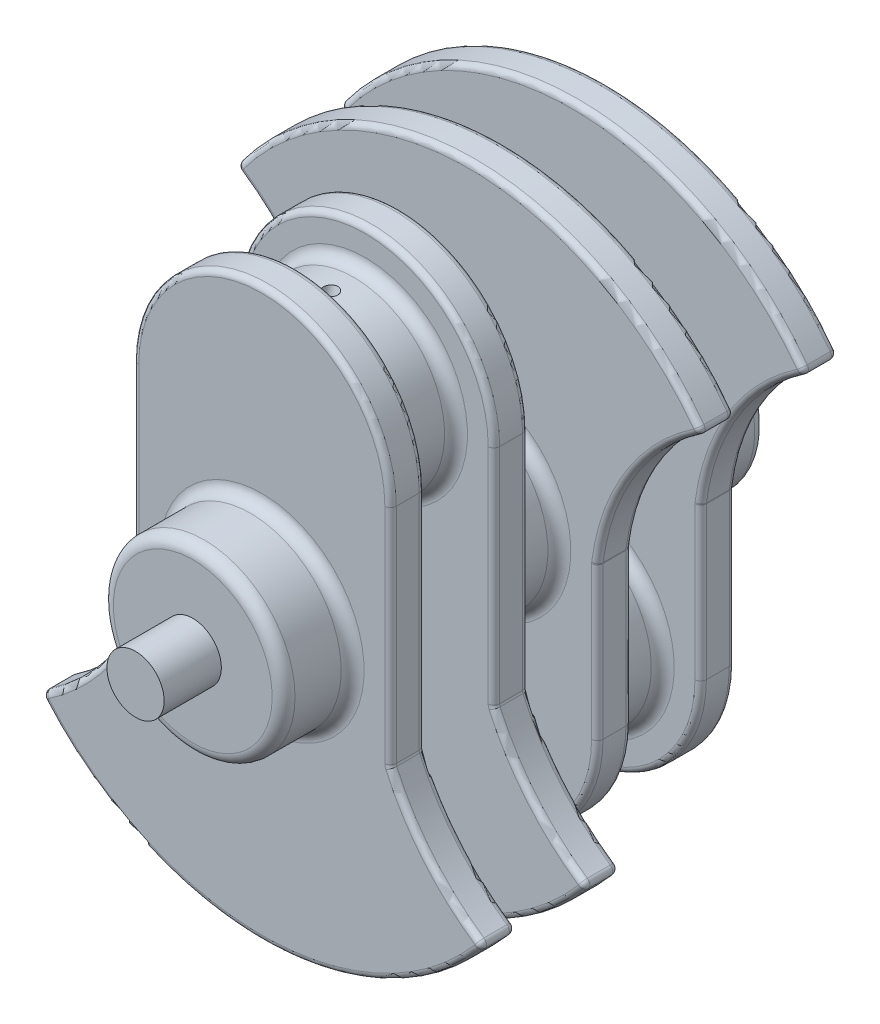
SolidWorks part; units mm, degrees
material "AISI 4340 Steel, normalized"
ref_plane "Front Plane" through (0, 0, 0) normal (0, 0, 1) x (1, 0, 0)
ref_plane "Top Plane" through (0, 0, 0) normal (0, 1, 0) x (1, 0, 0)
ref_plane "Right Plane" through (0, 0, 0) normal (1, 0, 0) x (0, 0, -1)
sketch "Sketch1" plane through (0, 0, 0) normal (0, 0, 1) x (1, 0, 0)
  circle A0 centre (0, 0) radius 31.75
  dimension "D1" = 31.75
extrude "Boss-Extrude1" add sketch "Sketch1" along normal blind 24.13
sketch "Sketch8" plane through (0, 0, 0) normal (0, 0, -1) x (-1, 0, 0)
  line L0 (-45, 53.333) -> (-45, -24.9419)
  line L1 (45, 53.333) -> (45, -24.9419)
  arc A0 (45, 53.333) -> (-45, 53.333) centre (0, 53.333) ccw
  arc A5 (-77.4745, -63.2274) -> (77.4745, -63.2274) centre (0, 0) ccw
  arc A6 (-45, -24.9419) -> (-77.4745, -63.2274) centre (-125, 10) cw
  arc A7 (45, -24.9419) -> (77.4745, -63.2274) centre (125, 10) ccw
  dimension "D1" = 45
  dimension "D2" = 100
  dimension "D3" = 53.333
  dimension "D5" = 10
  dimension "D6" = 125
extrude "Boss-Extrude5" add sketch "Sketch8" along normal blind 12
sketch "Sketch2" plane through (0, 0, 24.13) normal (0, 0, 1) x (1, 0, 0)
  circle A0 centre (0, 0) radius 10
  dimension "D1" = 10
extrude "Boss-Extrude2" add sketch "Sketch2" along normal blind 20
sketch "Sketch9" plane through (0, 0, -12) normal (0, 0, -1) x (-1, 0, 0)
  circle A0 centre (0, 53.333) radius 31.75
  dimension "D2" = 31.75
  dimension "D1" = 53.333
extrude "Boss-Extrude6" add sketch "Sketch9" along normal blind 24.13
ref_plane "Plane4" through (0, 0, -72.26) normal (0, 0, -1) x (-1, 0, 0)
sketch "Sketch10" plane through (0, 0, -36.13) normal (0, 0, -1) x (-1, 0, 0)
  line L0 (-45, -53.333) -> (-45, 0)
  line L1 (45, -53.333) -> (45, 0)
  arc A0 (-45, -53.333) -> (45, -53.333) centre (0, -53.333) ccw
  arc A1 (-45, 0) -> (-81.5321, 57.901) centre (-125, -10) ccw
  arc A2 (45, 0) -> (81.5321, 57.901) centre (125, -10) cw
  arc A3 (-81.5321, 57.901) -> (81.5321, 57.901) centre (0, 0) cw
  dimension "D1" = 45
  dimension "D5" = 10
  dimension "D3" = 100
  dimension "D2" = 53.333
  dimension "D4" = 125
extrude "Boss-Extrude7" add sketch "Sketch10" along normal blind 12 from surface starting at plane "Plane4"
ref_plane "Plane3" through (0, 0, -108.39) normal (0, 0, -1) x (-1, 0, 0)
sketch "Sketch12" plane through (0, 0, -108.39) normal (0, 0, -1) x (-1, 0, 0)
  line L2 (45, -53.333) -> (45, 0)
  line L3 (45, -53.333) -> (45, 0)
  line L4 (-45, 0) -> (-45, -53.333)
  line L5 (-45, 0) -> (-45, -53.333)
  arc A12 (-45, -53.333) -> (45, -53.333) centre (0, -53.333) ccw
  arc A13 (81.5321, 57.901) -> (45, 0) centre (125, -10) ccw
  arc A14 (81.5321, 57.901) -> (-81.5321, 57.901) centre (0, 0) ccw
  arc A15 (-45, 0) -> (-81.5321, 57.901) centre (-125, -10) ccw
  arc A16 (-45, -53.333) -> (45, -53.333) centre (0, -53.333) ccw
  arc A17 (81.5321, 57.901) -> (45, 0) centre (125, -10) ccw
  arc A18 (81.5321, 57.901) -> (-81.5321, 57.901) centre (0, 0) ccw
  arc A19 (-45, 0) -> (-81.5321, 57.901) centre (-125, -10) ccw
  dimension "D1" = 0
extrude "Boss-Extrude8" add sketch "Sketch12" along normal blind 12
sketch "Sketch14" plane through (0, 0, -84.26) normal (0, 0, -1) x (-1, 0, 0)
  circle A0 centre (0, -53.333) radius 31.75
  dimension "D2" = 31.75
  dimension "D1" = 53.333
extrude "Boss-Extrude9" add sketch "Sketch14" along normal up to next
sketch "Sketch15" plane through (0, 0, -120.39) normal (0, 0, -1) x (-1, 0, 0)
  circle A1 centre (0, 0) radius 31.75
  circle A2 centre (0, 0) radius 31.75
  dimension "D1" = 0
extrude "Boss-Extrude10" add sketch "Sketch15" along normal blind 24.13
sketch "Sketch16" plane through (0, 0, -144.52) normal (0, 0, -1) x (-1, 0, 0)
  circle A1 centre (0, 0) radius 10
  circle A2 centre (0, 0) radius 10
  dimension "D1" = 0
extrude "Boss-Extrude11" add sketch "Sketch16" along normal blind 20
sketch "Sketch18" plane through (0, 0, -36.13) normal (0, 0, -1) x (-1, 0, 0)
  line L2 (-45, 53.333) -> (-45, -24.9419)
  line L3 (-45, 53.333) -> (-45, -24.9419)
  line L4 (45, -24.9419) -> (45, 53.333)
  line L5 (45, -24.9419) -> (45, 53.333)
  arc A4 (45, 53.333) -> (-45, 53.333) centre (0, 53.333) ccw
  arc A5 (-77.4745, -63.2274) -> (-45, -24.9419) centre (-125, 10) ccw
  arc A6 (-77.4745, -63.2274) -> (77.4745, -63.2274) centre (0, 0) ccw
  arc A7 (45, -24.9419) -> (77.4745, -63.2274) centre (125, 10) ccw
  arc A8 (45, 53.333) -> (-45, 53.333) centre (0, 53.333) ccw
  arc A9 (-77.4745, -63.2274) -> (-45, -24.9419) centre (-125, 10) ccw
  arc A10 (-77.4745, -63.2274) -> (77.4745, -63.2274) centre (0, 0) ccw
  arc A11 (45, -24.9419) -> (77.4745, -63.2274) centre (125, 10) ccw
  dimension "D1" = 0
extrude "Boss-Extrude12" add sketch "Sketch18" along normal blind 12
sketch "Sketch19" plane through (0, 0, -48.13) normal (0, 0, -1) x (-1, 0, 0)
  circle A1 centre (0, 0) radius 31.75
  circle A2 centre (0, 0) radius 31.75
  dimension "D1" = 0
extrude "Boss-Extrude13" add sketch "Sketch19" along normal up to next
fillet "Fillet1" radius 2 32 edges at (0, -100, -36.13) (-58.4257, -46.4694, -36.13) (-45, 14.1956, -36.13) (45, 14.1956, -36.13) (58.4257, -46.4694, -36.13) (0, -100, -48.13) (-58.4257, -46.4694, -48.13) (-45, 14.1956, -48.13) (0, 98.333, -48.13) (45, 14.1956, -48.13) (58.4257, -46.4694, -48.13) (77.4745, -63.2274, -42.13) (45, -24.9419, -42.13) (-45, -24.9419, -42.13) (-77.4745, -63.2274, -42.13) (0, 98.333, -36.13) (45, 14.1956, 0) (58.4257, -46.4694, 0) (0, -100, 0) (-58.4257, -46.4694, 0) (-45, 14.1956, 0) (0, 98.333, -12) (45, 14.1956, -12) (58.4257, -46.4694, -12) (0, -100, -12) (-58.4257, -46.4694, -12) (-45, 14.1956, -12) (-45, -24.9419, -6) (-77.4745, -63.2274, -6) (77.4745, -63.2274, -6) (45, -24.9419, -6) (0, 98.333, 0)
fillet "Fillet2" radius 2 16 edges at (0, 100, -108.39) (56.8149, 33.0208, -108.39) (45, -26.6665, -108.39) (0, -98.333, -108.39) (-45, -26.6665, -108.39) (-56.8149, 33.0208, -108.39) (56.8149, 33.0208, -120.39) (45, -26.6665, -120.39) (0, -98.333, -120.39) (-45, -26.6665, -120.39) (-56.8149, 33.0208, -120.39) (-81.5321, 57.901, -114.39) (-45, 0, -114.39) (45, 0, -114.39) (81.5321, 57.901, -114.39) (0, 100, -120.39)
fillet "Fillet3" radius 2 16 edges at (45, -26.6665, -72.26) (56.8149, 33.0208, -72.26) (0, 100, -72.26) (-56.8149, 33.0208, -72.26) (-45, -26.6665, -72.26) (0, -98.333, -72.26) (45, -26.6665, -84.26) (56.8149, 33.0208, -84.26) (-56.8149, 33.0208, -84.26) (-45, -26.6665, -84.26) (0, -98.333, -84.26) (45, 0, -78.26) (81.5321, 57.901, -78.26) (-81.5321, 57.901, -78.26) (-45, 0, -78.26) (0, 100, -84.26)
fillet "Fillet5" radius 4 2 edges at (31.75, 0, 24.13) (31.75, 0, 0)
fillet "Fillet6" radius 4 2 edges at (-31.75, 0, -120.39) (-31.75, 0, -144.52)
ref_plane "Plane5" through (0, 31.75, 0) normal (0, 1, 0) x (1, 0, 0)
sketch "Sketch20" plane through (0, 0, 0) normal (1, 0, 0) x (0, 0, -1)
  line L1 (84.26, -85.083) -> (84.26, -21.583)
  line L2 (84.26, -85.083) -> (84.26, -21.583)
  dimension "D1" = 0
ref_plane "Plane6" through (0, -85.083, 0) normal (0, 1, 0) x (1, 0, 0)
sketch "Sketch21" plane through (0, 31.75, 0) normal (0, 1, 0) x (1, 0, 0)
  line L2 (-31.75, 140.52) -> (31.75, 140.52) construction
  line L3 (-31.75, 140.52) -> (-31.75, 124.39) construction
  line L4 (-31.75, 124.39) -> (31.75, 124.39) construction
  line L5 (31.75, 140.52) -> (31.75, 124.39) construction
  circle A0 centre (0, 132.455) radius 2.5
  point P10 (0, 140.52)
  point P11 (31.75, 132.455)
  dimension "D1" = 5
sketch "Sketch27" plane through (0, 0, 0) normal (0, 0, 1) x (1, 0, 0)
  line L0 (0, 85.083) -> (0, -31.75) construction
  circle A1 centre (0, 53.333) radius 31.75
  circle A2 centre (0, 53.333) radius 31.75 construction
  circle A3 centre (0, 0) radius 31.75
  circle A4 centre (0, 0) radius 31.75 construction
  dimension "D1" = 0
  dimension "D2" = 0
ref_plane "Plane8" through (0, 85.083, 0) normal (0, -1, 0) x (-1, 0, 0)
ref_plane "Plane9" through (0, -31.75, 0) normal (0, -1, 0) x (-1, 0, 0)
sketch "Sketch28" plane through (0, -31.75, 0) normal (0, -1, 0) x (-1, 0, 0)
  line L1 (-31.75, -4) -> (31.75, -4) construction
  line L2 (-31.75, -4) -> (-31.75, -20.13) construction
  line L3 (-31.75, -20.13) -> (31.75, -20.13) construction
  line L4 (31.75, -4) -> (31.75, -20.13) construction
  line L5 (-31.75, -4) -> (31.75, -20.13) construction
  line L6 (-31.75, -20.13) -> (31.75, -4) construction
  circle A0 centre (0, -12.065) radius 2.5
  point P4 (0, -12.065)
  dimension "D1" = 5
sketch "Sketch29" plane through (0, 85.083, 0) normal (0, -1, 0) x (-1, 0, 0)
  line L1 (31.75, 36.13) -> (-31.75, 36.13) construction
  line L2 (31.75, 36.13) -> (31.75, 12) construction
  line L3 (31.75, 12) -> (-31.75, 12) construction
  line L4 (-31.75, 36.13) -> (-31.75, 12) construction
  line L5 (31.75, 36.13) -> (-31.75, 12) construction
  line L6 (31.75, 12) -> (-31.75, 36.13) construction
  circle A0 centre (0, 24.065) radius 2.5
  point P4 (0, 24.065)
sketch "Sketch31" plane through (0, 0, 0) normal (1, 0, 0) x (0, 0, -1)
  line L0 (24.065, 85.083) -> (-12.065, -31.75) construction
ref_plane "Plane10" through (0, 85.083, -24.065) normal (0, -0.9554, 0.2954) x (-1, 0, 0)
ref_plane "Plane11" through (0, -31.75, 12.065) normal (0, -0.9554, 0.2954) x (-1, 0, 0)
combine bodies "Combine1" operation type add bodies to combine 119 109 117
fillet "Fillet7" radius 4 6 edges at (-31.75, 53.333, -36.13) (-31.75, 53.333, -12) (-31.75, 0, -48.13) (-31.75, 0, -72.26) (-31.75, -53.333, -108.39) (-31.75, -53.333, -84.26)
sketch "Sketch39" plane through (0, -85.083, 0) normal (0, 1, 0) x (1, 0, 0)
  line L1 (31.75, 104.39) -> (-31.75, 104.39) construction
  line L2 (31.75, 104.39) -> (31.75, 88.26) construction
  line L3 (31.75, 88.26) -> (-31.75, 88.26) construction
  line L4 (-31.75, 104.39) -> (-31.75, 88.26) construction
  line L5 (31.75, 104.39) -> (-31.75, 88.26) construction
  line L6 (31.75, 88.26) -> (-31.75, 104.39) construction
  point P4 (0, 96.325)
sketch "Sketch40" plane through (0, 0, 0) normal (1, 0, 0) x (0, 0, -1)
  line L0 (132.455, 31.75) -> (96.325, -85.083) construction
  line L1 (140.52, 31.75) -> (124.39, 31.75) construction
ref_plane "Plane12" through (0, 31.75, -132.455) normal (0, -0.9554, 0.2954) x (-1, 0, 0)
ref_plane "Plane13" through (0, -85.083, -96.325) normal (0, -0.9554, 0.2954) x (-1, 0, 0)
sketch "Sketch47" plane through (0, 85.083, -24.065) normal (0, -0.9554, 0.2954) x (-1, 0, 0)
  ellipse E0 centre (0, 0) end of major axis (2.5, 0) minor radius 2.3884 construction
  ellipse E1 centre (0, 0) end of major axis (2.5, 0) minor radius 2.3884
extrude "Cut-Extrude1" cut sketch "Sketch47" along normal through all
sketch "Sketch48" plane through (0, -31.75, 12.065) normal (0, -0.9554, 0.2954) x (-1, 0, 0)
  ellipse E0 centre (0, 0) end of major axis (2.5, 0) minor radius 2.3884 construction
  ellipse E1 centre (0, 0) end of major axis (2.5, 0) minor radius 2.3884
extrude "Cut-Extrude2" cut sketch "Sketch48" against normal through all
sketch "Sketch49" plane through (0, -85.083, -96.325) normal (0, -0.9554, 0.2954) x (-1, 0, 0)
  circle A0 centre (0, 0) radius 2.5
  dimension "D1" = 5
extrude "Cut-Extrude3" cut sketch "Sketch49" against normal through all
sketch "Sketch50" plane through (0, 31.75, -132.455) normal (0, -0.9554, 0.2954) x (-1, 0, 0)
  circle A0 centre (0, 0) radius 2.5 construction
  circle A1 centre (0, 0) radius 2.5
extrude "Cut-Extrude4" cut sketch "Sketch50" along normal through all
equation "\"CR\"= 53.333mm'Crank Radius"
equation "\"D1@Sketch9\"=\"CR\""
equation "\"D1@Sketch14\"=\"CR\""
equation "\"JR\"= 31.75mm'Journal Radius"
equation "\"D1@Sketch1\"=\"JR\""
equation "\"D2@Sketch9\"=\"JR\""
equation "\"D2@Sketch14\"=\"JR\""
equation "\"LT\"= 12mm'Lobe Thickness"
equation "\"D1@Boss-Extrude5\"=\"LT\""
equation "\"D1@Boss-Extrude7\"=\"LT\""
equation "\"D1@Boss-Extrude8\"=\"LT\""
equation "\"D1@Boss-Extrude12\"=\"LT\""
equation "\"D3@Sketch8\"=\"CR\""
equation "\"D2@Sketch10\"=\"CR\""
equation "\"JL\"= 24.13mm'Journal Length"
equation "\"D1@Boss-Extrude1\"=\"JL\""
equation "\"D1@Boss-Extrude6\"=\"JL\""
equation "\"D1@Boss-Extrude10\"=\"JL\""
equation "\"LHD\"= 5mm'Lubrication Hole Diameter"
equation "\"D1@Sketch29\"=\"LHD\""
